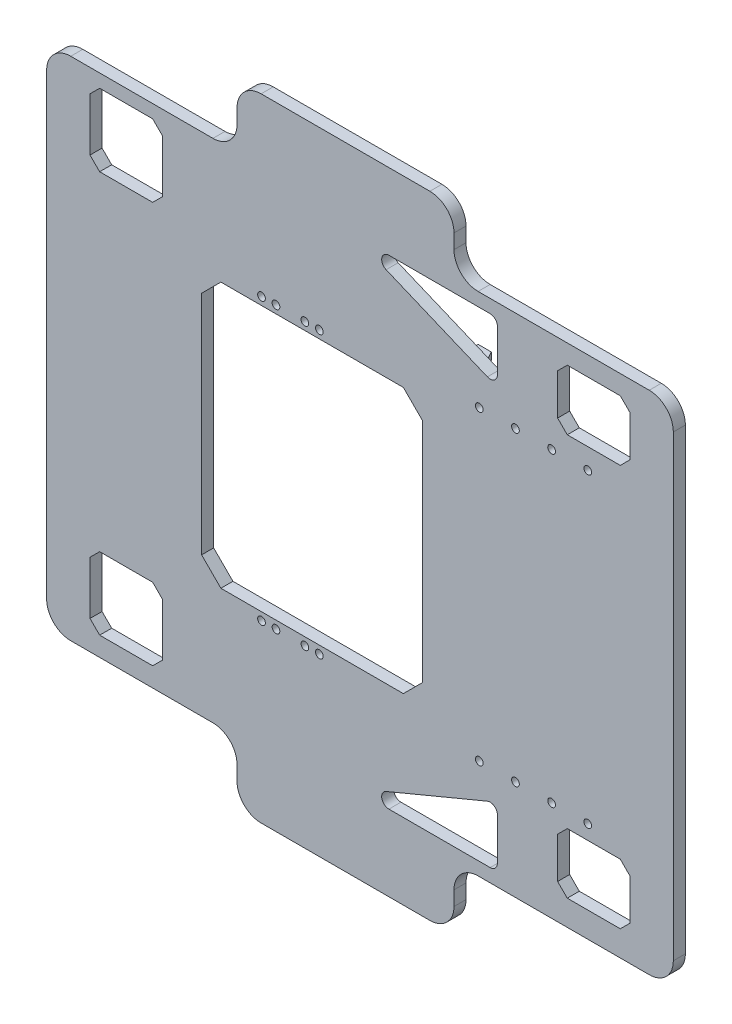
SolidWorks part; units mm, degrees
ref_plane "前视基准面" through (0, 0, 0) normal (0, 0, 1) x (1, 0, 0)
ref_plane "上视基准面" through (0, 0, 0) normal (0, 1, 0) x (1, 0, 0)
ref_plane "右视基准面" through (0, 0, 0) normal (1, 0, 0) x (0, 0, -1)
sketch "草图1" plane through (0, 0, 0) normal (0, 0, 1) x (1, 0, 0)
  line L0 (-51, 115) -> (-51, 121)
  line L1 (-120, 105) -> (-61, 105)
  line L2 (-130, 95) -> (-130, -95)
  line L3 (-120, -105) -> (-61, -105)
  line L4 (130, 95) -> (130, -95)
  line L5 (-130, 105) -> (-126.7518, 102.3765) construction
  line L6 (-130, -105) -> (-126.7518, -102.3765) construction
  line L7 (-41, 131) -> (29, 131)
  line L8 (39, 121) -> (39, 115)
  line L9 (-51, -115) -> (-51, -121)
  line L10 (-41, -131) -> (29, -131)
  line L11 (39, -121) -> (39, -115)
  line L12 (49, 105) -> (120, 105)
  line L13 (49, -105) -> (120, -105)
  line L14 (126.7518, -102.3765) -> (130, -105) construction
  line L15 (126.7518, 102.3765) -> (130, 105) construction
  arc A0 (-130, 95) -> (-120, 105) centre (-120, 95) cw
  arc A1 (-120, -105) -> (-130, -95) centre (-120, -95) cw
  arc A2 (130, 95) -> (120, 105) centre (120, 95) ccw
  arc A3 (120, -105) -> (130, -95) centre (120, -95) ccw
  arc A4 (-61, 105) -> (-51, 115) centre (-61, 115) ccw
  arc A5 (49, 105) -> (39, 115) centre (49, 115) cw
  arc A6 (-41, 131) -> (-51, 121) centre (-41, 121) ccw
  arc A7 (39, 121) -> (29, 131) centre (29, 121) ccw
  arc A8 (-51, -115) -> (-61, -105) centre (-61, -115) ccw
  arc A9 (39, -115) -> (49, -105) centre (49, -115) cw
  arc A10 (-41, -131) -> (-51, -121) centre (-41, -121) cw
  arc A11 (29, -131) -> (39, -121) centre (29, -121) ccw
  point P0 (0, 0)
  point P28 (-45.35, 105)
  point P32 (39, 105)
  point P40 (39, -105)
  dimension "D1" = 10
  dimension "D2" = 10
  dimension "D3" = 10
  dimension "D4" = 10
  dimension "D5" = 10
  dimension "D6" = 10
  dimension "D9" = 10
  dimension "D11" = 10
  dimension "D7" = 10
  dimension "D8" = 10
  dimension "D10" = 10
  dimension "D12" = 10
  dimension "D13" = 210
  dimension "D14" = 59
  dimension "D15" = 71
  dimension "D16" = 59
  dimension "D17" = 71
  dimension "D18" = 70
  dimension "D19" = 6
  dimension "D20" = 6
extrude "凸台-拉伸1" add sketch "草图1" along normal blind 5
sketch "草图2" plane through (0, 0, 5) normal (0, 0, 1) x (1, 0, 0)
  line L0 (130, -95) -> (130, 95) construction
  line L5 (10.8462, -93.7308) -> (52.8462, -76.2308)
  line L6 (-108, 99.5) -> (-86, 99.5)
  line L7 (-108, -67) -> (-86, -67)
  line L8 (-112, -71) -> (-112, -93)
  line L9 (-108, -97) -> (-86, -97)
  line L10 (-82, -71) -> (-82, -93)
  line L11 (-112, -67) -> (-82, -97) construction
  line L12 (-112, -97) -> (-82, -67) construction
  line L13 (86, 97) -> (108, 97)
  line L14 (82, 93) -> (82, 76)
  line L15 (86, 72) -> (108, 72)
  line L16 (112, 93) -> (112, 76)
  line L17 (82, 97) -> (112, 72) construction
  line L18 (82, 72) -> (112, 97) construction
  line L19 (86, -69.5) -> (108, -69.5)
  line L20 (82, -73.5) -> (82, -90.5)
  line L21 (86, -94.5) -> (108, -94.5)
  line L22 (112, -73.5) -> (112, -90.5)
  line L23 (82, -69.5) -> (112, -94.5) construction
  line L24 (82, -94.5) -> (112, -69.5) construction
  line L25 (12, 99.5) -> (54, 99.5)
  line L28 (57, 96.5) -> (57, 79)
  line L29 (10.8462, 93.7308) -> (52.8462, 76.2308)
  line L33 (12, -99.5) -> (54, -99.5)
  line L34 (57, -79) -> (57, -96.5)
  line L35 (-41, -131) -> (29, -131) construction
  line L37 (-112, 95.5) -> (-112, 73.5)
  line L38 (-120, -105) -> (-61, -105) construction
  line L39 (-130, 95) -> (-130, -95) construction
  line L40 (-108, 69.5) -> (-86, 69.5)
  line L41 (-82, 95.5) -> (-82, 73.5)
  line L42 (-112, 99.5) -> (-82, 69.5) construction
  line L43 (-112, 69.5) -> (-82, 99.5) construction
  line L44 (-112, 73.5) -> (-108, 69.5)
  line L45 (-112, 95.5) -> (-108, 99.5)
  line L46 (-86, 69.5) -> (-82, 73.5)
  line L47 (-86, 99.5) -> (-82, 95.5)
  line L48 (-108, -67) -> (-112, -71)
  line L49 (-112, -93) -> (-108, -97)
  line L50 (-86, -67) -> (-82, -71)
  line L51 (-86, -97) -> (-82, -93)
  line L52 (86, 97) -> (82, 93)
  line L53 (82, 76) -> (86, 72)
  line L54 (108, 97) -> (112, 93)
  line L55 (108, 72) -> (112, 76)
  line L56 (86, -69.5) -> (82, -73.5)
  line L57 (108, -69.5) -> (112, -73.5)
  line L58 (82, -90.5) -> (86, -94.5)
  line L59 (108, -94.5) -> (112, -90.5)
  arc A0 (57, -96.5) -> (54, -99.5) centre (54, -96.5) cw
  arc A1 (57, -79) -> (52.8462, -76.2308) centre (54, -79) ccw
  arc A2 (12, -99.5) -> (10.8462, -93.7308) centre (12, -96.5) cw
  arc A3 (10.8462, 93.7308) -> (12, 99.5) centre (12, 96.5) cw
  arc A4 (57, 96.5) -> (54, 99.5) centre (54, 96.5) ccw
  arc A5 (57, 79) -> (52.8462, 76.2308) centre (54, 79) cw
  point P0 (-97, 84.5)
  point P1 (-97, 84.5)
  point P5 (-97, -82)
  point P10 (97, 84.5)
  point P15 (97, -82)
  point P20 (27, 84.5)
  point P25 (27, -82)
  point P75 (-3, 99.5)
  point P78 (57, 99.5)
  dimension "D11" = 3
  dimension "D17" = 3
  dimension "D18" = 3
  dimension "D35" = 3
  dimension "D36" = 3
  dimension "D37" = 3
  dimension "D2" = 8
  dimension "D3" = 18
  dimension "D4" = 30
  dimension "D5" = 25
  dimension "D6" = 30
  dimension "D7" = 18
  dimension "D8" = 18
  dimension "D9" = 25
  dimension "D10" = 30
  dimension "D12" = 60
  dimension "D13" = 25
  dimension "D14" = 30
  dimension "D15" = 25
  dimension "D19" = 42
  dimension "D20" = 17.5
  dimension "D38" = 17.5
  dimension "D39" = 31.5
extrude "切除-拉伸1" cut sketch "草图2" against normal through all
sketch "草图3" plane through (0, 0, 0) normal (0, 0, -1) x (-1, 0, 0)
  line L0 (130, 95) -> (130, -95) construction
  line L1 (57.7, 55) -> (-18, 55)
  line L2 (65.7, 47) -> (65.7, -47)
  line L3 (57.7, -55) -> (-18, -55)
  line L4 (-26, 47) -> (-26, -47)
  line L5 (65.7, 55) -> (-26, -55) construction
  line L6 (65.7, -55) -> (-26, 55) construction
  line L7 (-26, -47) -> (-18, -55)
  line L8 (-18, 55) -> (-26, 47)
  line L9 (65.7, -47) -> (57.7, -55)
  line L10 (57.7, 55) -> (65.7, 47)
  point P0 (19.85, 0)
  dimension "D1" = 64.3
  dimension "D2" = 91.7
  dimension "D3" = 110
extrude "切除-拉伸2" cut sketch "草图3" against normal through all
sketch "草图4" plane through (0, 0, 0) normal (0, 0, -1) x (-1, 0, 0)
  line L0 (-29, -55) -> (-29, -66)
  line L1 (-29, -66) -> (-40, -66)
  line L2 (-40, -66) -> (-40, -63)
  line L3 (-40, -63) -> (-32, -63)
  line L4 (-32, -63) -> (-32, -55)
  line L5 (-32, -55) -> (-29, -55)
  line L6 (-26, 47) -> (-26, -47) construction
  line L7 (-49, -105) -> (-120, -105) construction
  dimension "D1" = 11
  dimension "D2" = 11
  dimension "D3" = 3
  dimension "D4" = 3
  dimension "D5" = 3
  dimension "D6" = 39
extrude "凸台-拉伸2" add sketch "草图4" along normal blind 15
sketch "草图5" plane through (0, -66, 0) normal (0, -1, 0) x (1, 0, 0)
  line L0 (40, -5) -> (34.5, -15)
  line L1 (40, -15) -> (40, 0) construction
  line L2 (40, -15) -> (29, -15) construction
  line L3 (34.5, -15) -> (40, -15)
  line L4 (40, -15) -> (40, -5)
  dimension "D1" = 10
  dimension "D2" = 5.5
extrude "切除-拉伸3" cut sketch "草图5" against normal blind 10
sketch "草图6" plane through (29, 0, 0) normal (-1, 0, 0) x (0, 0, 1)
  line L0 (-15, -60.5) -> (-5, -55)
  line L1 (-15, -66) -> (-15, -55) construction
  line L2 (-15, -55) -> (0, -55) construction
  line L3 (-5, -55) -> (-15, -55)
  line L4 (-15, -55) -> (-15, -60.5)
  dimension "D1" = 10
  dimension "D2" = 5.5
extrude "切除-拉伸4" cut sketch "草图6" against normal blind 10
ref_plane "基准面2" through (72, 0, 0) normal (-1, 0, 0) x (0, 0, 1)
mirror "镜向1" about plane through (72, 0, 0) normal (-1, 0, 0) of "凸台-拉伸2", "切除-拉伸3", "切除-拉伸4"
mirror "镜向2" about plane through (0, 0, 0) normal (0, 1, 0) of "镜向1"
sketch "草图7" plane through (0, 0, 0) normal (0, 0, -1) x (-1, 0, 0)
  line L0 (65.7, -47) -> (65.7, 47) construction
  line L1 (-18, -55) -> (57.7, -55) construction
  circle A0 centre (16.85, -58.25) radius 1.6
  circle A1 centre (22.85, -58.25) radius 1.6
  circle A2 centre (40.85, -58.25) radius 1.6
  circle A3 centre (34.85, -58.25) radius 1.6
  dimension "D1" = 3.2
  dimension "D2" = 3.2
  dimension "D3" = 3.2
  dimension "D4" = 3.2
  dimension "D6" = 6
  dimension "D7" = 6
  dimension "D8" = 30.85
  dimension "D9" = 3.25
  dimension "D5" = 18
extrude "切除-拉伸5" cut sketch "草图7" against normal through all
mirror "镜向3" about plane through (0, 0, 0) normal (0, 1, 0) of "切除-拉伸5"
sketch "草图8" plane through (0, 0, 0) normal (0, 0, -1) x (-1, 0, 0)
  line L1 (-40, -63) -> (-40, -66) construction
  circle A0 centre (-49.5, -63.4954) radius 1.6
  circle A1 centre (-64.5, -63.4954) radius 1.6
  circle A2 centre (-79.5, -63.4954) radius 1.6
  circle A3 centre (-94.5, -63.4954) radius 1.6
  dimension "D1" = 3.2
  dimension "D2" = 3.2
  dimension "D3" = 3.2
  dimension "D4" = 3.2
  dimension "D5" = 15
  dimension "D6" = 15
  dimension "D7" = 15
  dimension "D8" = 9.5
extrude "切除-拉伸6" cut sketch "草图8" against normal through all
mirror "镜向4" about plane through (0, 0, 0) normal (0, 1, 0) of "切除-拉伸6"
equation "\"45、\"=43.7672"
